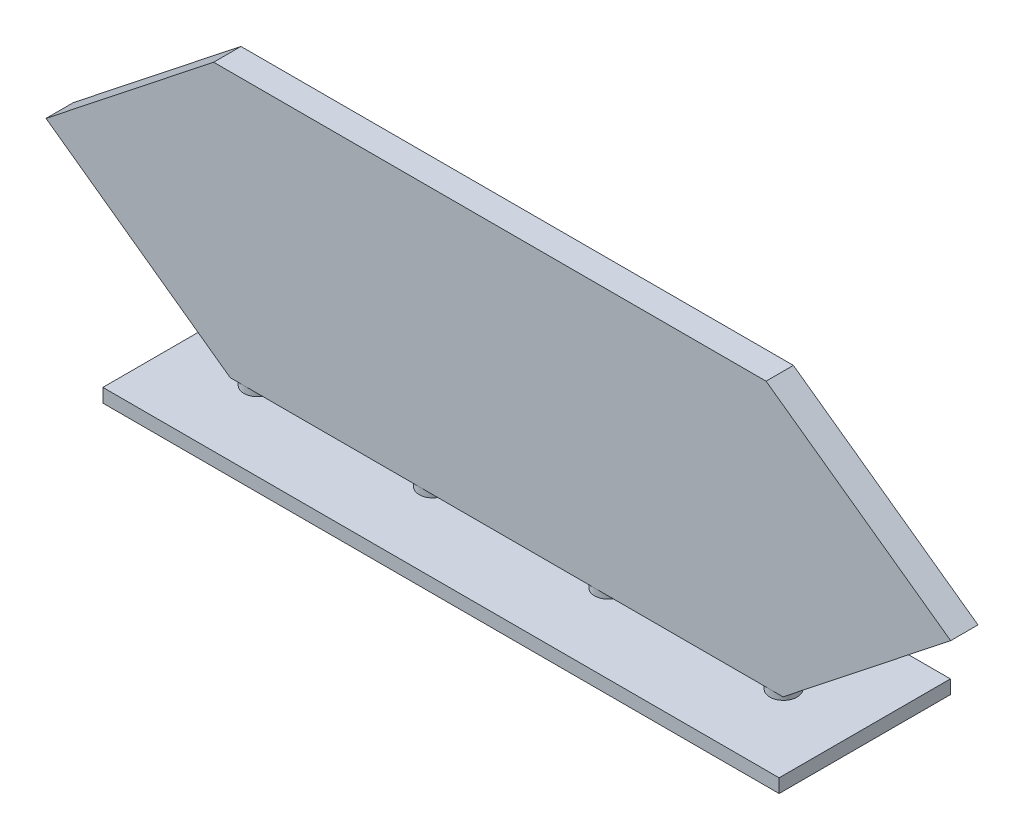
SolidWorks part; units mm, degrees
ref_plane "Спереди" through (0, 0, 0) normal (0, 0, 1) x (1, 0, 0)
ref_plane "Сверху" through (0, 0, 0) normal (0, 1, 0) x (1, 0, 0)
ref_plane "Справа" through (0, 0, 0) normal (1, 0, 0) x (0, 0, -1)
sketch "Эскиз1" plane through (0, 0, 0) normal (0, 0, 1) x (1, 0, 0)
  line L0 (-12.687, 6.1823) -> (-20.5304, -0.015)
  line L1 (-20.5304, -0.015) -> (-11.9055, -6.2172)
  line L2 (-11.9055, -6.2172) -> (12.6423, -6.2172)
  line L3 (12.6423, -6.2172) -> (20.5304, 0.0154)
  line L4 (20.5304, 0.0154) -> (11.8866, 6.2172)
  line L5 (11.8866, 6.2172) -> (-13.7612, 6.2172)
  line L6 (-13.7612, 6.2172) -> (-12.687, 6.1823)
extrude "Бобышка-Вытянуть1" add sketch "Эскиз1" along normal blind 1.2
sketch "Эскиз2" plane through (0, 0, 1.2) normal (0, 0, 1) x (1, 0, 0)
  line L0 (-12.687, 6.1823) -> (-13.7612, 6.2172)
  line L1 (-13.7612, 6.2172) -> (-12.6427, 6.2172)
  line L2 (11.8866, 6.2172) -> (-13.7612, 6.2172) construction
  line L3 (-12.6427, 6.2172) -> (-12.687, 6.1823)
  line L4 (-12.687, 6.1823) -> (-20.5304, -0.015) construction
extrude "Вырез-Вытянуть1" cut sketch "Эскиз2" against normal blind 1.2
sketch "Эскиз3" plane through (0, 0, 1.2) normal (0, 0, 1) x (1, 0, 0)
  line L6 (11.8866, 6.2172) -> (-12.6427, 6.2172)
  line L7 (-12.6427, 6.2172) -> (-20.5304, -0.015)
  line L8 (-20.5304, -0.015) -> (-11.9055, -6.2172)
  line L9 (-11.9055, -6.2172) -> (12.6423, -6.2172)
  line L10 (12.6423, -6.2172) -> (20.5304, 0.0154)
  line L11 (20.5304, 0.0154) -> (11.8866, 6.2172)
  line L12 (11.8866, 6.2172) -> (-12.6427, 6.2172)
  line L13 (-12.6427, 6.2172) -> (-20.5304, -0.015)
  line L14 (-20.5304, -0.015) -> (-11.9055, -6.2172)
  line L15 (-11.9055, -6.2172) -> (12.6423, -6.2172)
  line L16 (12.6423, -6.2172) -> (20.5304, 0.0154)
  line L17 (20.5304, 0.0154) -> (11.8866, 6.2172)
  dimension "D1" = 0
extrude "Вырез-Вытянуть-Тонкостенный1" cut sketch "Эскиз3" against normal blind 1.2 thin thin type one direction reverse wall 0.4
sketch "Эскиз4" plane through (0, -5.8172, 0) normal (0, -1, 0) x (1, 0, 0)
  line L0 (-11.7766, 0) -> (-11.7766, 1.2) construction
  line L1 (-11.7766, 0) -> (12.5033, 0) construction
  circle A0 centre (-11.1766, 0.6) radius 0.6
  circle A1 centre (-3.4766, 0.6) radius 0.6
  circle A2 centre (4.2234, 0.6) radius 0.6
  circle A3 centre (11.9234, 0.6) radius 0.6
  dimension "D1" = 1.2
  dimension "D2" = 0.6
  dimension "D3" = 0.6
  dimension "D4" = 4
extrude "Бобышка-Вытянуть2" add sketch "Эскиз4" along normal blind 0.3
sketch "Эскиз5" plane through (0, -6.1172, 0) normal (0, -1, 0) x (1, 0, 0)
  line L1 (-14.5033, 4.0649) -> (15.1959, 4.0649)
  line L2 (-14.5033, 4.0649) -> (-14.5033, -3.4589)
  line L3 (-14.5033, -3.4589) -> (15.1959, -3.4589)
  line L4 (15.1959, 4.0649) -> (15.1959, -3.4589)
extrude "Бобышка-Вытянуть3" add sketch "Эскиз5" along normal blind 0.6
